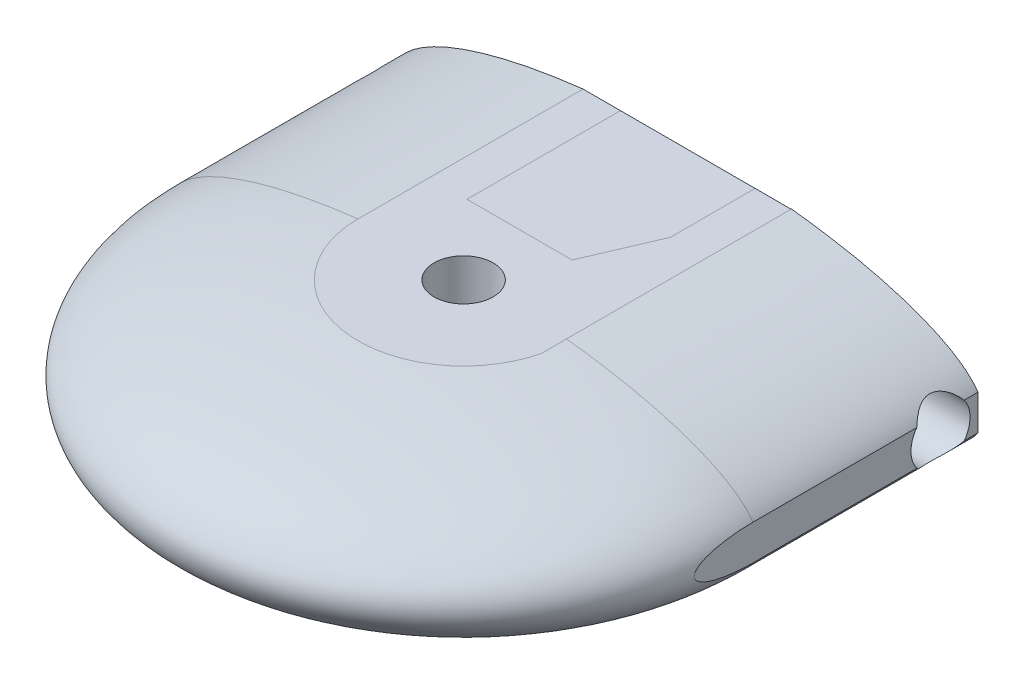
SolidWorks part; units mm, degrees
other "COLL.BOX-Boss-Extrude3"
ref_plane "Front Plane" through (0, 0, 0) normal (0, 0, 1) x (1, 0, 0)
ref_plane "Top Plane" through (0, 0, 0) normal (0, 1, 0) x (1, 0, 0)
ref_plane "Right Plane" through (0, 0, 0) normal (1, 0, 0) x (0, 0, -1)
sketch "Sketch1" plane through (0, 0, 0) normal (0, 1, 0) x (1, 0, 0)
  circle A0 centre (0, 0) radius 26.9875
  circle A1 centre (0, 0) radius 28.575
  dimension "D1" = 53.975
  dimension "D2" = 57.15
extrude "Boss-Extrude1" add sketch "Sketch1" along normal blind 67
sketch "Sketch2" plane through (0, 0, 0) normal (0, 0, 1) x (1, 0, 0)
  line L0 (-50, 33.5) -> (50, 33.5)
  line L1 (0, 48.5) -> (0, 18.5)
  ellipse E0 centre (0, 33.5) end of major axis (50, 33.5) minor radius 15
  dimension "D1" = 30
  dimension "D2" = 100
extrude "Boss-Extrude2" add sketch "Sketch2" along normal blind 76.2 and the other way blind 76.2 contours L1 E0 L0 | L0 E0 L1 | L1 E0 L0 | L0 E0 L1 region at (-21.2207, 39.8662, 0) region at (-21.2207, 27.1338, 0) region at (21.2207, 39.8662, 0) region at (21.2207, 27.1338, 0)
sketch "Sketch4" plane through (0, 67, 0) normal (0, 1, 0) x (1, 0, 0)
  circle A0 centre (0, 0) radius 25.4
extrude "Cut-Extrude1" cut sketch "Sketch4" against normal blind 76.2
sketch "Sketch7" plane through (0, 67, 0) normal (0, 1, 0) x (1, 0, 0)
  line L1 (29.9358, -17.9247) -> (27.2202, -17.9247)
  line L2 (29.9358, -17.9247) -> (29.9358, 20.5522)
  line L3 (29.9358, 20.5522) -> (27.2202, 20.5522)
  line L4 (27.2202, -17.9247) -> (27.2202, 20.5522)
extrude "Cut-Extrude2" cut sketch "Sketch7" against normal blind 10.2
sketch "Sketch10" plane through (0, 0, 76.2) normal (0, 0, 1) x (1, 0, 0)
  line L0 (0, 48.5) -> (0, 18.5)
  line L1 (20.801, 47.1403) -> (20.801, 19.8597)
  arc A0 (20.801, 19.8597) -> (20.801, 47.1403) centre (0, 33.5) ccw
  ellipse E1 centre (0, 33.5) end of major axis (50, 33.5) minor radius 15
  ellipse E2 centre (0, 33.5) end of major axis (50, 33.5) minor radius 15
  dimension "D1" = 0
revolve "Revolve2" add sketch "Sketch10" angle 360 about L0 region at (10.2402, 33.5, 76.2) region at (22.4424, 33.5, 76.2) region at (34.409, 33.5, 76.2)
mirror "Mirror2" about plane through (0, 0, 0) normal (0, 0, 1) of "Revolve2"
sketch "Sketch11" plane through (0, 67, 0) normal (0, 1, 0) x (1, 0, 0)
  line L1 (0, 76.2) -> (50, 76.2) construction
  circle A0 centre (0, -76.2) radius 5
  circle A1 centre (0, 76.2) radius 5
  dimension "D1" = 10
  dimension "D2" = 10
  dimension "D3" = 76.2
  dimension "D4" = 76.2
extrude "Cut-Extrude4" cut sketch "Sketch11" against normal blind 80
sketch "Sketch13" plane through (0, 0, 0) normal (1, 0, 0) x (0, 0, -1)
  circle A0 centre (-44.45, 33.5) radius 5
  dimension "D1" = 10
  dimension "D2" = 44.45
extrude "Cut-Extrude6" cut sketch "Sketch13" against normal blind 80 and the other way blind 84
mirror "Mirror3" about plane through (0, 0, 0) normal (0, 0, 1) of "Cut-Extrude6"
sketch "Sketch12" plane through (0, 0, 0) normal (0, 1, 0) x (1, 0, 0)
  line L1 (-55.9723, 152.8439) -> (53.5701, 152.8439)
  line L2 (-55.9723, 152.8439) -> (-55.9723, -38.1)
  line L3 (-55.9723, -38.1) -> (53.5701, -38.1)
  line L4 (53.5701, 152.8439) -> (53.5701, -38.1)
  dimension "D1" = 38.1
extrude "Cut-Extrude5" cut sketch "Sketch12" against normal blind 30 and the other way blind 116
sketch "Sketch14" plane through (0, 0, 38.1) normal (0, 0, -1) x (-1, 0, 0)
  line L0 (0, 48.5) -> (0, 18.5)
  line L1 (-17.4131, 52.1195) -> (17.8779, 52.1195)
  line L2 (-17.4131, 52.1195) -> (-17.4131, 47.5084)
  line L3 (-17.4131, 47.5084) -> (17.8779, 47.5084)
  line L4 (17.8779, 52.1195) -> (17.8779, 47.5084)
  line L5 (49, 42.7343) -> (59.3355, 42.7343)
  line L6 (49, 42.7343) -> (49, 24.321)
  line L7 (49, 24.321) -> (59.3355, 24.321)
  line L8 (59.3355, 42.7343) -> (59.3355, 24.321)
  line L9 (-59.3355, 42.7343) -> (-59.3355, 24.321)
  line L10 (-49, 24.321) -> (-59.3355, 24.321)
  line L11 (-49, 42.7343) -> (-49, 24.321)
  line L12 (-49, 42.7343) -> (-59.3355, 42.7343)
  line L13 (-50, 33.5) -> (50, 33.5)
  line L14 (17.8779, 14.8805) -> (17.8779, 19.4916)
  line L15 (-17.4131, 19.4916) -> (17.8779, 19.4916)
  line L16 (-17.4131, 14.8805) -> (-17.4131, 19.4916)
  line L17 (-17.4131, 14.8805) -> (17.8779, 14.8805)
  ellipse E0 centre (0, 33.5) end of major axis (-50, 33.5) minor radius 15 construction
  ellipse M4 centre (0, 33.5) end of major axis (-50, 33.5) minor radius 15
  dimension "D1" = 49
extrude "Cut-Extrude7" cut sketch "Sketch14" against normal blind 80 contours L2 L3 L0 M4 | L0 L3 M4 | L11 L12 L9 L10 M4 | L13 L11 M4 | L13 L11 M4 | L16 L0 L15 M4 | L13 L6 M4 | L6 L13 M4 | L8 L5 L6 L7 M4 | L15 L14 L17 L16 region at (-6.7348, 47.9062, 38.1) region at (6.7236, 47.9066, 38.1) region at (-49.4003, 34.6209, 38.1) region at (-54.2698, 33.5282, 38.1) region at (54.2698, 33.5282, 38.1) region at (49.4003, 34.6209, 38.1) region at (6.7236, 19.0934, 38.1) region at (49.4003, 32.3791, 38.1) region at (-49.4003, 32.3791, 38.1)
sketch "Sketch15" plane through (0, 0, 38.1) normal (0, 0, -1) x (-1, 0, 0)
  line L0 (-17.4131, 47.5084) -> (17.8779, 47.5084) construction
  line L1 (11.5331, 47.5084) -> (-11.2633, 47.5084)
  line L2 (11.5331, 47.5084) -> (11.5331, 19.4916)
  line L3 (11.5331, 19.4916) -> (-11.2633, 19.4916)
  line L4 (-11.2633, 47.5084) -> (-11.2633, 19.4916)
  line L5 (-17.4131, 19.4916) -> (17.8779, 19.4916) construction
extrude "Boss-Extrude3" add sketch "Sketch15" against normal blind 26 separate body
equation "\"d1\"= 1.5cm'membrane smaller diameter"
equation "\"r0\"= 1.5in'membrane circular radius"
equation "\"d2\"= sqr ( 2 * \"r0\" ^ 2 - \"d1\" ^ 2 )'membrane larger radius"
